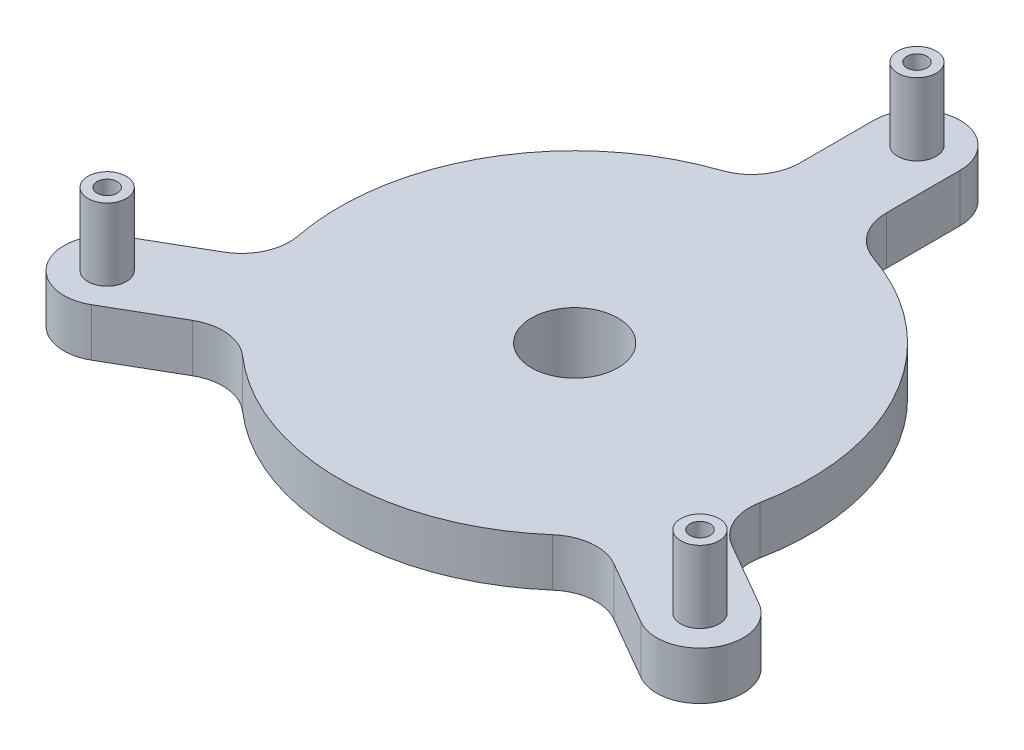
SolidWorks part; units mm, degrees
ref_plane "前基準面" through (0, 0, 0) normal (0, 0, 1) x (1, 0, 0)
ref_plane "上基準面" through (0, 0, 0) normal (0, 1, 0) x (1, 0, 0)
ref_plane "右基準面" through (0, 0, 0) normal (1, 0, 0) x (0, 0, -1)
sketch "草圖1" plane through (0, 0, 0) normal (0, 1, 0) x (1, 0, 0)
  circle A0 centre (0, 0) radius 82.5
  circle A1 centre (0, 0) radius 9
  dimension "D1" = 165
  dimension "D2" = 18
extrude "填料-伸長1" add sketch "草圖1" along normal blind 5
sketch "草圖2" plane through (0, 5, 0) normal (0, 1, 0) x (1, 0, 0)
  line L0 (0, 0) -> (0, 82.5) construction
  line L1 (0, 0) -> (71.4471, -41.25) construction
  line L2 (0, 0) -> (-71.4471, -41.25) construction
  circle A0 centre (0, 0) radius 82.5 construction
  circle A1 centre (0, 71.25) radius 4
  circle A2 centre (61.7043, -35.625) radius 4
  circle A3 centre (-61.7043, -35.625) radius 4
  circle A4 centre (0, 71.25) radius 2.1
  circle A5 centre (61.7043, -35.625) radius 2.1
  circle A6 centre (-61.7043, -35.625) radius 2.1
  point P15 (0, 0)
  point P22 (0, 0)
  dimension "D1" = 8
  dimension "D6" = 4.2
  dimension "D2" = 3
  dimension "D3" = 71.25
  dimension "D4" = 1.9
  dimension "D5" = 3
extrude "填料-伸長2" add sketch "草圖2" along normal blind 15
sketch "草圖3" plane through (0, 0, 0) normal (0, -1, 0) x (1, 0, 0)
  circle A0 centre (0, 0) radius 9 construction
  circle A1 centre (0, 0) radius 9
  circle A2 centre (0, 0) radius 31.5
  dimension "D2" = 63
  dimension "D1" = 22.5
extrude "填料-伸長3" add sketch "草圖3" along normal blind 5
sketch "草圖4" plane through (0, 5, 0) normal (0, 1, 0) x (1, 0, 0)
  line L0 (-9, 71.25) -> (-9, 55.857)
  line L1 (9, 71.25) -> (9, 55.857)
  line L2 (66.2043, -27.8308) -> (52.8735, -20.1343)
  line L3 (57.2043, -43.4192) -> (43.8735, -35.7227)
  line L4 (-57.2043, -43.4192) -> (-43.8735, -35.7227)
  line L5 (-66.2043, -27.8308) -> (-52.8735, -20.1343)
  circle A0 centre (0, 0) radius 49 construction
  arc A1 (-15.7797, 46.3897) -> (-48.0645, -9.5293) centre (0, 0) ccw
  circle A2 centre (-61.7043, -35.625) radius 9
  arc A3 (-66.2043, -27.8308) -> (-57.2043, -43.4192) centre (-61.7043, -35.625) ccw
  arc A4 (48.0645, -9.5293) -> (15.7797, 46.3897) centre (0, 0) ccw
  arc A5 (-43.8735, -35.7227) -> (-32.2848, -36.8604) centre (-38.8735, -44.383) cw
  arc A6 (43.8735, -35.7227) -> (32.2848, -36.8604) centre (38.8735, -44.383) ccw
  arc A7 (52.8735, -20.1343) -> (48.0645, -9.5293) centre (57.8735, -11.474) cw
  arc A8 (9, 55.857) -> (15.7797, 46.3897) centre (19, 55.857) ccw
  arc A9 (-9, 55.857) -> (-15.7797, 46.3897) centre (-19, 55.857) cw
  arc A10 (-52.8735, -20.1343) -> (-48.0645, -9.5293) centre (-57.8735, -11.474) ccw
  circle A11 centre (0, 71.25) radius 9
  arc A12 (9, 71.25) -> (-9, 71.25) centre (0, 71.25) ccw
  circle A13 centre (0, 0) radius 9 construction
  circle A14 centre (61.7043, -35.625) radius 9
  arc A15 (57.2043, -43.4192) -> (66.2043, -27.8308) centre (61.7043, -35.625) ccw
  circle A16 centre (0, 0) radius 9
  arc A17 (-32.2848, -36.8604) -> (32.2848, -36.8604) centre (0, 0) ccw
  circle A18 centre (0, 0) radius 82.5 construction
  circle A19 centre (0, 0) radius 82.5
  point P28 (0, 0)
  point P35 (-9, 48.1664)
  circle M24 centre (0, 0) radius 82.5
  dimension "D7" = 10
  dimension "D5" = 18
  dimension "D1" = 5
  dimension "D2" = 5
  dimension "D3" = 5
  dimension "D4" = 40
  dimension "D6" = 3
extrude "除料-伸長1" cut sketch "草圖4" against normal blind 10 and the other way through all contours A17 A5 L4 A3 L5 A10 A1 A9 L0 A12 L1 A8 A4 A7 L2 A15 L3 A6 M24 region at (-80.1665, 5, 0)
sketch "草圖5" plane through (0, 0, 0) normal (0, -1, 0) x (1, 0, 0)
  line L6 (-43.8735, 35.7227) -> (-57.2043, 43.4192)
  line L7 (-66.2043, 27.8308) -> (-52.8735, 20.1343)
  line L8 (-9, -55.857) -> (-9, -71.25)
  line L9 (9, -71.25) -> (9, -55.857)
  line L10 (52.8735, 20.1343) -> (66.2043, 27.8308)
  line L11 (57.2043, 43.4192) -> (43.8735, 35.7227)
  line L12 (-43.8735, 35.7227) -> (-57.2043, 43.4192)
  line L13 (-66.2043, 27.8308) -> (-52.8735, 20.1343)
  line L14 (-9, -55.857) -> (-9, -71.25)
  line L15 (9, -71.25) -> (9, -55.857)
  line L16 (52.8735, 20.1343) -> (66.2043, 27.8308)
  line L17 (57.2043, 43.4192) -> (43.8735, 35.7227)
  circle A0 centre (0, 0) radius 46
  arc A13 (32.2848, 36.8604) -> (-32.2848, 36.8604) centre (0, 0) ccw
  arc A14 (-43.8735, 35.7227) -> (-32.2848, 36.8604) centre (-38.8735, 44.383) ccw
  arc A15 (-57.2043, 43.4192) -> (-66.2043, 27.8308) centre (-61.7043, 35.625) ccw
  arc A16 (-48.0645, 9.5293) -> (-52.8735, 20.1343) centre (-57.8735, 11.474) ccw
  arc A17 (-48.0645, 9.5293) -> (-15.7797, -46.3897) centre (0, 0) ccw
  arc A18 (-9, -55.857) -> (-15.7797, -46.3897) centre (-19, -55.857) ccw
  arc A19 (-9, -71.25) -> (9, -71.25) centre (0, -71.25) ccw
  arc A20 (15.7797, -46.3897) -> (9, -55.857) centre (19, -55.857) ccw
  arc A21 (15.7797, -46.3897) -> (48.0645, 9.5293) centre (0, 0) ccw
  arc A22 (52.8735, 20.1343) -> (48.0645, 9.5293) centre (57.8735, 11.474) ccw
  arc A23 (66.2043, 27.8308) -> (57.2043, 43.4192) centre (61.7043, 35.625) ccw
  arc A24 (32.2848, 36.8604) -> (43.8735, 35.7227) centre (38.8735, 44.383) ccw
  arc A25 (32.2848, 36.8604) -> (-32.2848, 36.8604) centre (0, 0) ccw
  arc A26 (-43.8735, 35.7227) -> (-32.2848, 36.8604) centre (-38.8735, 44.383) ccw
  arc A27 (-57.2043, 43.4192) -> (-66.2043, 27.8308) centre (-61.7043, 35.625) ccw
  arc A28 (-48.0645, 9.5293) -> (-52.8735, 20.1343) centre (-57.8735, 11.474) ccw
  arc A29 (-48.0645, 9.5293) -> (-15.7797, -46.3897) centre (0, 0) ccw
  arc A30 (-9, -55.857) -> (-15.7797, -46.3897) centre (-19, -55.857) ccw
  arc A31 (-9, -71.25) -> (9, -71.25) centre (0, -71.25) ccw
  arc A32 (15.7797, -46.3897) -> (9, -55.857) centre (19, -55.857) ccw
  arc A33 (15.7797, -46.3897) -> (48.0645, 9.5293) centre (0, 0) ccw
  arc A34 (52.8735, 20.1343) -> (48.0645, 9.5293) centre (57.8735, 11.474) ccw
  arc A35 (66.2043, 27.8308) -> (57.2043, 43.4192) centre (61.7043, 35.625) ccw
  arc A36 (32.2848, 36.8604) -> (43.8735, 35.7227) centre (38.8735, 44.383) ccw
  dimension "D1" = 0
  dimension "D2" = 92
extrude "填料-伸長4" add sketch "草圖5" along normal up to surface (5 mm away) contours A25 A26 L12 A27 L13 A28 A29 A30 L14 A31 L15 A32 A33 A34 L16 A35 L17 A36 up to face at (0, -5, -31.5)
sketch "草圖6" plane through (0, 0, 0) normal (0, 1, 0) x (1, 0, 0)
  circle A1 centre (0, 0) radius 9
  circle A2 centre (0, 0) radius 9
  dimension "D1" = 0
extrude "除料-伸長2" cut sketch "草圖6" against normal through all
sketch "草圖7" plane through (0, -5, 0) normal (0, -1, 0) x (1, 0, 0)
  circle A0 centre (0, 0) radius 34.75
  circle A1 centre (0, 0) radius 9 construction
  circle A2 centre (0, 0) radius 9
  dimension "D1" = 69.5
extrude "填料-伸長5" add sketch "草圖7" along normal blind 5
